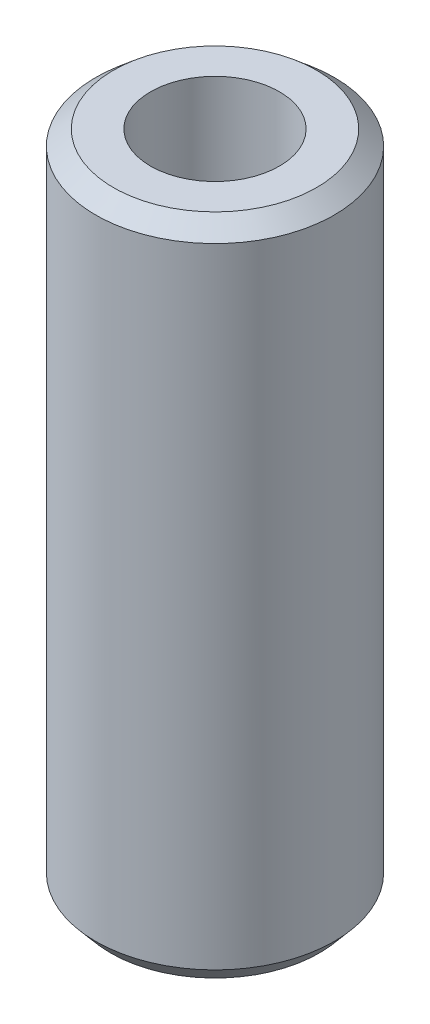
SolidWorks part; units mm, degrees
ref_plane "Front Plane" through (0, 0, 0) normal (0, 0, 1) x (1, 0, 0)
ref_plane "Top Plane" through (0, 0, 0) normal (0, 1, 0) x (1, 0, 0)
ref_plane "Right Plane" through (0, 0, 0) normal (1, 0, 0) x (0, 0, -1)
sketch "Sketch1" plane through (0, 0, 0) normal (0, 1, 0) x (1, 0, 0)
  circle A0 centre (0, 0) radius 10
  dimension "SHAFT_OD" = 20
extrude "Boss-Extrude1" add sketch "Sketch1" along normal blind 55.4762
sketch "Sketch2" plane through (0, 0, 0) normal (0, 1, 0) x (1, 0, 0)
  circle A0 centre (0, 0) radius 5.4048
  dimension "BORE_D" = 10.8095
extrude "Cut-Extrude1" cut sketch "Sketch2" along normal through all
chamfer "Chamfer1" distance 1.2559 angle 49.627 2 edges at (0, 55.4762, 10) (0, 0, 10) first distance on face at (0, 55.4762, 10) first distance on face at (0, 0, 5.4048)
